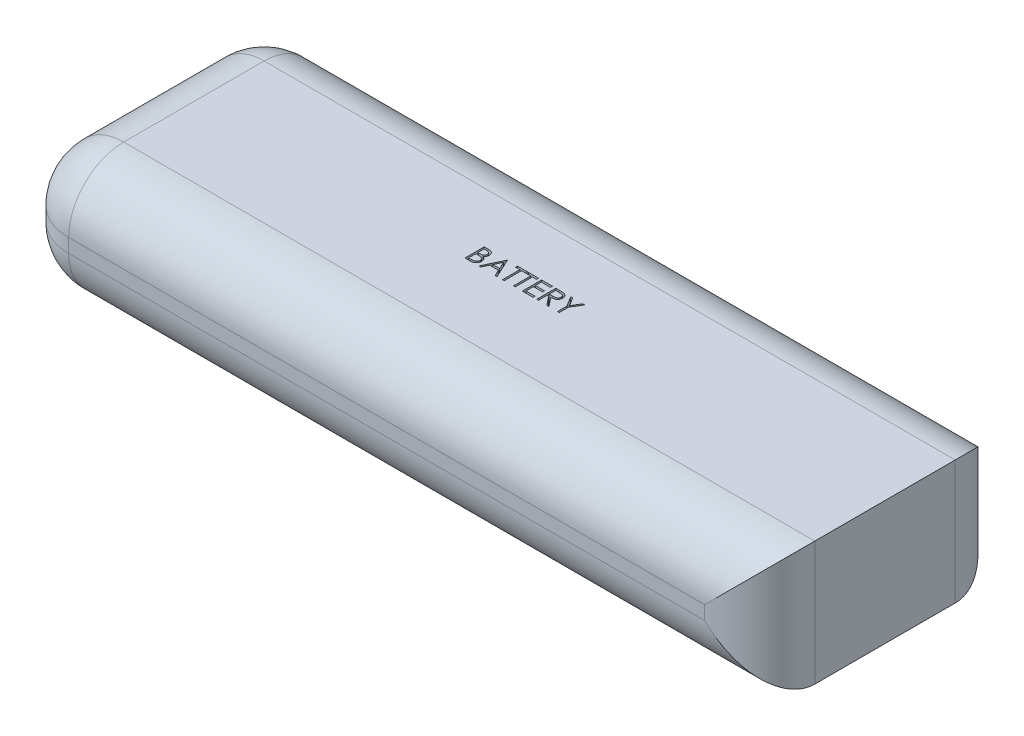
SolidWorks part; units mm, degrees
ref_plane "Front Plane" through (0, 0, 0) normal (0, 0, 1) x (1, 0, 0)
ref_plane "Top Plane" through (0, 0, 0) normal (0, 1, 0) x (1, 0, 0)
ref_plane "Right Plane" through (0, 0, 0) normal (1, 0, 0) x (0, 0, -1)
sketch "Sketch1" plane through (0, 0, 0) normal (0, 1, 0) x (1, 0, 0)
  line L1 (-67.75, -22.75) -> (67.75, -22.75)
  line L2 (-67.75, -22.75) -> (-67.75, 22.75)
  line L3 (-67.75, 22.75) -> (67.75, 22.75)
  line L4 (67.75, -22.75) -> (67.75, 22.75)
  line L5 (-67.75, -22.75) -> (67.75, 22.75) construction
  line L6 (-67.75, 22.75) -> (67.75, -22.75) construction
  point P0 (0, 0)
  dimension "D1" = 135.5
  dimension "D2" = 45.5
extrude "Boss-Extrude1" add sketch "Sketch1" along normal blind 22.5
sketch "Sketch2" plane through (0, 22.5, 0) normal (0, 1, 0) x (1, 0, 0)
  line L0 (-66.8227, 0) -> (67.75, 0) construction
  line L1 (67.75, -22.75) -> (67.75, 22.75) construction
  text T0 "BATTERY"
extrude "Cut-Extrude1" cut sketch "Sketch2" against normal blind 12.7
fillet "Fillet2" radius 10 8 edges at (67.75, 11.25, -22.75) (0, 22.5, -22.75) (-67.75, 11.25, -22.75) (0, 0, -22.75) (-67.75, 11.25, 22.75) (0, 22.5, 22.75) (67.75, 11.25, 22.75) (0, 0, 22.75)
fillet "Fillet3" radius 10 6 edges at (-64.8211, 2.9289, -19.8211) (-64.8211, 2.9289, 19.8211) (-64.8211, 19.5711, -19.8211) (-64.8211, 19.5711, 19.8211) (-67.75, 0, 0) (-67.75, 22.5, 0)
